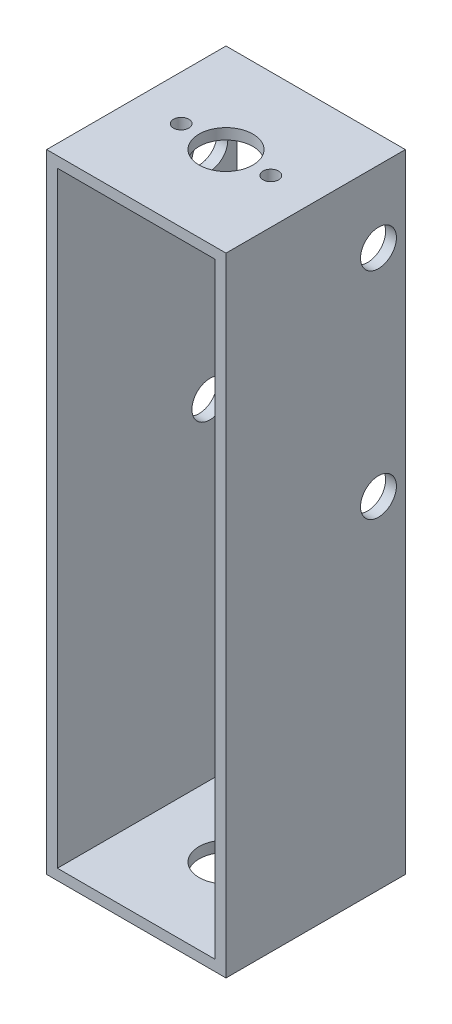
SolidWorks part; units mm, degrees
ref_plane "Front Plane" through (0, 0, 0) normal (0, 0, 1) x (1, 0, 0)
ref_plane "Top Plane" through (0, 0, 0) normal (0, 1, 0) x (1, 0, 0)
ref_plane "Right Plane" through (0, 0, 0) normal (1, 0, 0) x (0, 0, -1)
sketch "Sketch1" plane through (0, 0, 0) normal (0, 1, 0) x (1, 0, 0)
  line L1 (25, -25) -> (-25, -25)
  line L2 (25, -25) -> (25, 25)
  line L3 (25, 25) -> (-25, 25)
  line L4 (-25, -25) -> (-25, 25)
  line L5 (25, -25) -> (-25, 25) construction
  line L6 (25, 25) -> (-25, -25) construction
  point P0 (0, 0)
  dimension "D1" = 50
extrude "Boss-Extrude1" add sketch "Sketch1" against normal blind 175
shell "Shell1" thickness 3 removed face at (0, -87.5, -25) removed face at (0, -87.5, 25)
sketch "Sketch2" plane through (0, 0, 0) normal (0, 1, 0) x (1, 0, 0)
  circle A0 centre (0, 0) radius 7.5
  circle A2 centre (-12.5, 0) radius 2.15
  arc A3 (-14.15, 0) -> (-10.85, 0) centre (-12.5, 0) ccw construction
  circle A4 centre (12.5, 0) radius 2.15
  dimension "D1" = 15
  dimension "D2" = 0.5
extrude "Cut-Extrude1" cut sketch "Sketch2" against normal up to next
extrude "Cut-Extrude2" cut sketch "Sketch2<2>" against normal through all contours A0
sketch "Sketch2<2>" plane through (0, 0, 0) normal (0, 1, 0) x (1, 0, 0) same geometry as "Sketch2"
sketch "Sketch3" plane through (25, 0, 0) normal (1, 0, 0) x (0, 0, -1)
  line L0 (17.5, 0) -> (17.5, -175) construction
  line L2 (-25, 0) -> (25, 0) construction
  line L3 (-25, -175) -> (25, -175) construction
  line L4 (7.5, 0) -> (-7.5, 0) construction
  line L5 (-7.5, 0) -> (7.5, 0) construction
  line L6 (-7.5, 0) -> (-7.5, -175) construction
  line L7 (-7.5, -175) -> (7.5, -175) construction
  line L8 (7.5, 0) -> (7.5, -175) construction
  circle A0 centre (17.5, -20) radius 5
  circle A1 centre (17.5, -80) radius 5
  dimension "D1" = 5
  dimension "D4" = 10
  dimension "D2" = 20
  dimension "D3" = 80
extrude "Cut-Extrude3" cut sketch "Sketch3" against normal through all
